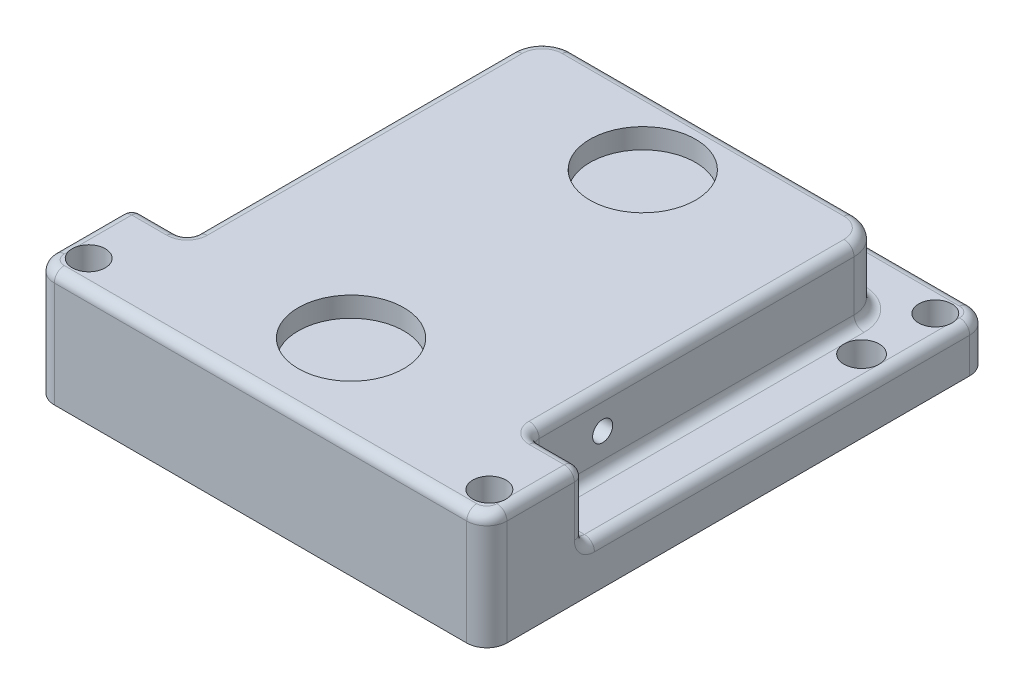
SolidWorks part; units mm, degrees
ref_plane "前视基准面" through (0, 0, 0) normal (0, 0, 1) x (1, 0, 0)
ref_plane "上视基准面" through (0, 0, 0) normal (0, 1, 0) x (1, 0, 0)
ref_plane "右视基准面" through (0, 0, 0) normal (1, 0, 0) x (0, 0, -1)
sketch "草图1" plane through (0, 0, 0) normal (0, 1, 0) x (1, 0, 0)
  line L1 (-22.5, 25) -> (22.5, 25)
  line L2 (-22.5, 25) -> (-22.5, -25)
  line L3 (-22.5, -25) -> (22.5, -25)
  line L4 (22.5, 25) -> (22.5, -25)
  line L5 (-22.5, 25) -> (22.5, -25) construction
  line L6 (-22.5, -25) -> (22.5, 25) construction
  point P0 (0, 0)
  dimension "D1" = 45
  dimension "D2" = 50
extrude "凸台-拉伸1" add sketch "草图1" along normal blind 4.5
sketch "草图3" plane through (0, 0, 0) normal (0, -1, 0) x (1, 0, 0)
  line L8 (17.5, -20) -> (17.5, 20)
  line L9 (17.5, 20) -> (-17.5, 20)
  line L10 (-17.5, 20) -> (-17.5, -20)
  line L11 (-17.5, -20) -> (17.5, -20)
  line L12 (17.5, -18) -> (17.5, 18)
  line L13 (15.5, 20) -> (-15.5, 20)
  line L14 (-17.5, 18) -> (-17.5, -18)
  line L15 (-15.5, -20) -> (15.5, -20)
  arc A0 (-17.5, -18) -> (-15.5, -20) centre (-15.5, -18) ccw
  arc A1 (17.5, -18) -> (15.5, -20) centre (15.5, -18) cw
  arc A2 (17.5, 18) -> (15.5, 20) centre (15.5, 18) ccw
  arc A3 (-15.5, 20) -> (-17.5, 18) centre (-15.5, 18) ccw
  dimension "D2" = 2
  dimension "D1" = 5
fillet "圆角2" radius 2 4 edges at (-22.5, 2.25, 25) (22.5, 2.25, 25) (22.5, 2.25, -25) (-22.5, 2.25, -25)
extrude "切除-拉伸1" cut sketch "草图3" against normal offset from surface (4 mm away) 0.5 up to face at (0, 4.5, 0)
sketch "草图4" plane through (0, 4.5, 0) normal (0, -1, 0) x (1, 0, 0)
  line L1 (-17, 15.3) -> (-17, -20)
  line L3 (17, -20) -> (17, 15.3)
  line L4 (13, -18) -> (13, 11.3)
  line L5 (13, 11.3) -> (-13, 11.3)
  line L6 (-13, 11.3) -> (-13, -18)
  line L7 (-13, -18) -> (13, -18)
  line L8 (13, -18) -> (13, 11.3) construction
  line L9 (13, 11.3) -> (-13, 11.3) construction
  line L10 (-13, 11.3) -> (-13, -18) construction
  line L11 (-13, -18) -> (13, -18) construction
  line L16 (-17, -20) -> (17, -20)
  line L17 (17, -22) -> (17, 15.3) construction
  line L18 (-17, 15.3) -> (-17, -22) construction
  line L19 (-17, 15.3) -> (17, 15.3)
  line L20 (-17, -22) -> (17, -22) construction
  line L23 (17, 15.3) -> (-17, 15.3) construction
  dimension "D3" = 4
  dimension "D4" = 4
  dimension "D2" = 4
  dimension "D1" = 0
extrude "凸台-拉伸2" add sketch "草图4" against normal blind 7
sketch "草图6" plane through (0, 4.5, 0) normal (0, 1, 0) x (1, 0, 0)
  line L1 (-22.5, 23) -> (-22.5, -23) construction
  line L2 (-20.5, -25) -> (20.5, -25) construction
  line L3 (22.5, -23) -> (22.5, 23) construction
  line L4 (16, -15.3) -> (-16, -15.3)
  line L5 (-22.5, -15.3) -> (-22.5, -23)
  line L6 (-20.5, -25) -> (20.5, -25)
  line L7 (22.5, -23) -> (22.5, -15.3)
  line L8 (16, -15.3) -> (22.5, -15.3)
  line L9 (-16, -15.3) -> (-22.5, -15.3)
  line L10 (17, -15.3) -> (-17, -15.3) construction
  arc A0 (-22.5, -23) -> (-20.5, -25) centre (-20.5, -23) ccw construction
  arc A1 (20.5, -25) -> (22.5, -23) centre (20.5, -23) ccw construction
  arc A2 (-22.5, -23) -> (-20.5, -25) centre (-20.5, -23) ccw
  arc A3 (20.5, -25) -> (22.5, -23) centre (20.5, -23) ccw
extrude "凸台-拉伸3" add sketch "草图6" along normal up to surface (7 mm away) up to face at (0, 11.5, -2.35)
sketch "草图5" plane through (0, 4, 0) normal (0, -1, 0) x (1, 0, 0)
  line L0 (7.5, 12.8) -> (-10, 12.8)
  line L1 (-14.5, 12.8) -> (-14.5, -19)
  line L3 (14.5, -19) -> (14.5, 12.8)
  line L4 (17, -20) -> (17, 15.3)
  line L5 (-17, -20) -> (17, -20)
  line L6 (-17, 15.3) -> (-17, -20)
  line L7 (-15.5, -20) -> (15.5, -20) construction
  line L8 (17, -17.9873) -> (17, 15.3) construction
  line L10 (-17, 15.3) -> (-17, -17.9873) construction
  line L15 (14.5, 12.8) -> (-14.5, 12.8) construction
  line L16 (14.5, 12.8) -> (14.5, 16.8)
  line L17 (13.5, 17.8) -> (8.5, 17.8)
  line L18 (7.5, 16.8) -> (7.5, 12.8)
  line L19 (-10, 12.8) -> (-14.5, 12.8)
  line L20 (-17, 15.3) -> (17, 15.3) construction
  line L22 (-14.5, 12.8) -> (-14.5, -17.5) construction
  line L23 (14.5, -17.5) -> (14.5, 12.8) construction
  line L24 (17, 15.3) -> (-17, 15.3) construction
  line L25 (-14.5, -19) -> (14.5, -19)
  line L26 (-22.5, 15.3) -> (-17, 15.3)
  line L27 (-22.5, 23) -> (-22.5, 15.3)
  line L30 (-17, 15.3) -> (-17, -20) construction
  line L31 (17, -20) -> (17, 15.3) construction
  line L32 (20.5, 25) -> (-20.5, 25)
  line L33 (22.5, 15.3) -> (22.5, 23)
  line L34 (-17, -20) -> (17, -20) construction
  line L35 (17, 15.3) -> (22.5, 15.3)
  line L36 (-14.5, -17.5) -> (14.5, -17.5) construction
  arc A2 (14.5, 16.8) -> (13.5, 17.8) centre (13.5, 16.8) ccw
  arc A3 (8.5, 17.8) -> (7.5, 16.8) centre (8.5, 16.8) ccw
  arc A6 (-20.5, 25) -> (-22.5, 23) centre (-20.5, 23) ccw
  arc A7 (22.5, 23) -> (20.5, 25) centre (20.5, 23) ccw
  point P10 (0, 0)
  point P26 (14.5, 17.8)
  point P31 (7.5, 17.8)
  dimension "D8" = 1
  dimension "D3" = 1
  dimension "D6" = 7
  dimension "D7" = 5
  dimension "D1" = 0
  dimension "D2" = 2.5
extrude "切除-拉伸2" cut sketch "草图5" against normal offset from surface (5 mm away) 2.5 up to face at (0, 11.5, 11.8028)
sketch "草图7" plane through (0, 11.5, 0) normal (0, 1, 0) x (1, 0, 0)
  circle A0 centre (-19.9142, 22.1642) radius 1.5008 construction
  circle A1 centre (19.9142, 22.1642) radius 1.5 construction
  circle A2 centre (-19.9142, -22.1642) radius 1.5008 construction
  circle A3 centre (19.9142, -22.1642) radius 1.5 construction
  circle A4 centre (-19.9142, 22.1642) radius 1.5008 construction
  circle A5 centre (19.9142, 22.1642) radius 1.5 construction
  circle A6 centre (-19.9142, -22.1642) radius 1.5008 construction
  circle A7 centre (19.9142, -22.1642) radius 1.5 construction
  circle A10 centre (-19.9142, -22.1642) radius 1.65
  circle A11 centre (19.9142, -22.1642) radius 1.65
  dimension "D1" = 3.3
extrude "切除-拉伸3" cut sketch "草图7" against normal through all
sketch "草图8" plane through (0, 4.5, 0) normal (0, 1, 0) x (1, 0, 0)
  circle A0 centre (19.9142, 22.1642) radius 1.5 construction
  circle A1 centre (-19.9142, 22.1642) radius 1.5008 construction
  circle A2 centre (19.9142, 22.1642) radius 1.5 construction
  circle A3 centre (-19.9142, 22.1642) radius 1.5008 construction
  circle A4 centre (19.9142, 22.1642) radius 1.65
  circle A5 centre (-19.9142, 22.1642) radius 1.65
  dimension "D1" = 3.3
  dimension "D2" = 3.3
extrude "切除-拉伸4" cut sketch "草图8" against normal through all
sketch "草图11" plane through (17, 0, 0) normal (1, 0, 0) x (0, 0, -1)
  line L0 (20, 11.5) -> (20, 4.5) construction
  line L1 (20, 4.5) -> (-15.3, 4.5) construction
  circle A1 centre (-7.9873, 8) radius 1
  dimension "D1" = 27.9873
  dimension "D2" = 3.5
extrude "切除-拉伸5" cut sketch "草图11" against normal through all
fillet "圆角4" radius 3 2 edges at (-17, 8, -20) (17, 8, -20)
fillet "圆角5" radius 1 27 edges at (-22.5, 4.5, -3.85) (-21.9142, 4.5, -24.4142) (0, 4.5, -25) (21.9142, 4.5, -24.4142) (22.5, 4.5, -3.85) (-17, 4.5, -0.85) (-16.1213, 4.5, -19.1213) (0, 4.5, -20) (16.1213, 4.5, -19.1213) (17, 11.5, -0.85) (16.1213, 11.5, -19.1213) (0, 11.5, -20) (-16.1213, 11.5, -19.1213) (22.5, 11.5, 19.15) (21.9142, 11.5, 24.4142) (-22.5, 11.5, 19.15) (-21.9142, 11.5, 24.4142) (17, 4.5, -0.85) (-22.5, 8, 15.3) (-17, 8, 15.3) (17, 8, 15.3) (22.5, 8, 15.3) (19.75, 4.5, 15.3) (19.75, 11.5, 15.3) (-17, 11.5, -0.85) (-19.75, 11.5, 15.3) (0, 11.5, 25)
sketch "草图12" plane through (0, 11.5, 0) normal (0, 1, 0) x (1, 0, 0)
  circle A0 centre (0, 13) radius 5.25
  circle A1 centre (0, -16) radius 5.25
  point P4 (0, 0)
  point P8 (-0.8553, -5.4588)
  dimension "D3" = 10.5
  dimension "D1" = 13
  dimension "D2" = 16
extrude "切除-拉伸6" cut sketch "草图12" against normal blind 2
sketch "草图14" plane through (0, 4.5, 0) normal (0, 1, 0) x (1, 0, 0)
  arc A4 (-18, 15) -> (-21.5, 15) centre (-19.75, 15) ccw construction
  arc A5 (-21.5, 15) -> (-18, 15) centre (-19.75, 15) ccw construction
  arc A6 (21.5, 15) -> (18, 15) centre (19.75, 15) ccw construction
  arc A7 (18, 15) -> (21.5, 15) centre (19.75, 15) ccw construction
  circle A8 centre (-19.75, 15) radius 1.75
  circle A9 centre (19.75, 15) radius 1.75
  dimension "D1" = 3.5
  dimension "D2" = 3.5
extrude "切除-拉伸8" cut sketch "草图14" against normal blind 2.5
